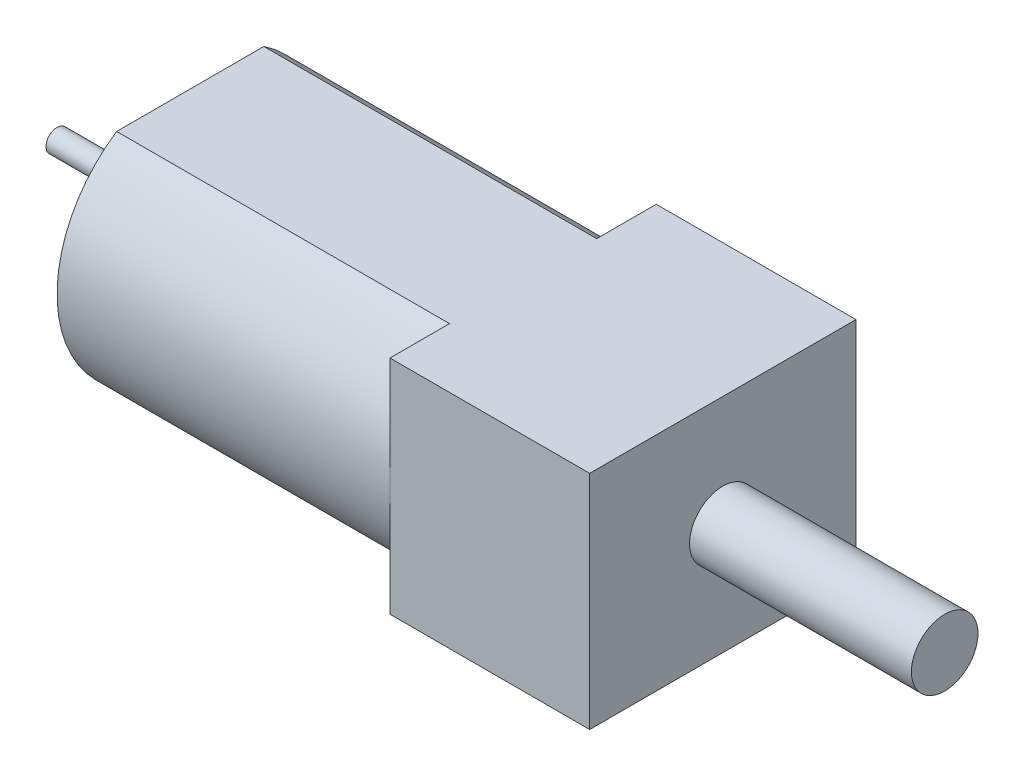
SolidWorks part; units mm, degrees
ref_plane "Front Plane" through (0, 0, 0) normal (0, 0, 1) x (1, 0, 0)
ref_plane "Top Plane" through (0, 0, 0) normal (0, 1, 0) x (1, 0, 0)
ref_plane "Right Plane" through (0, 0, 0) normal (1, 0, 0) x (0, 0, -1)
sketch "Sketch2" plane through (0, 0, 0) normal (1, 0, 0) x (0, 0, -1)
  line L1 (0, 0) -> (12, 0)
  line L2 (0, 0) -> (0, 10)
  line L3 (0, 10) -> (12, 10)
  line L4 (12, 0) -> (12, 10)
  dimension "D1" = 12
  dimension "D2" = 10
extrude "Boss-Extrude1" add sketch "Sketch2" along normal blind 24
sketch "Sketch3" plane through (24, 0, 0) normal (1, 0, 0) x (0, 0, -1)
  circle A0 centre (6, 5) radius 1.5
  point P0 (6, 5)
extrude "Boss-Extrude2" add sketch "Sketch3" along normal blind 10
sketch "Sketch4" plane through (0, 0, 0) normal (-1, 0, 0) x (0, 0, 1)
  line L0 (-12, 10) -> (0, 10) construction
  circle A0 centre (-6, 5) radius 6
  point P2 (-9.3166, 10)
  point P3 (-2.6834, 10)
  point P6 (-2.6834, 0)
  point P7 (-9.3166, 0)
  dimension "D1" = 12
extrude "Cut-Extrude1" cut sketch "Sketch4" against normal blind 15 flip side to cut
sketch "Sketch5" plane through (0, 0, 0) normal (-1, 0, 0) x (0, 0, 1)
  circle A0 centre (-6, 5) radius 0.5
  point P0 (-6, 5)
  dimension "D1" = 1
extrude "Boss-Extrude3" add sketch "Sketch5" along normal blind 6
sketch "Sketch6" plane through (34, 0, 0) normal (1, 0, 0) x (0, 0, -1)
  point P0 (6, 5)
sketch "Sketch7" plane through (-6, 0, 0) normal (-1, 0, 0) x (0, 0, 1)
  point P0 (-6, 5)
ref_axis "Axis1" through (-6, 5, -6) along (1, 0, 0)
ref_axis "Axis2" through (0, 10, -6) along (1, 0, 0)
